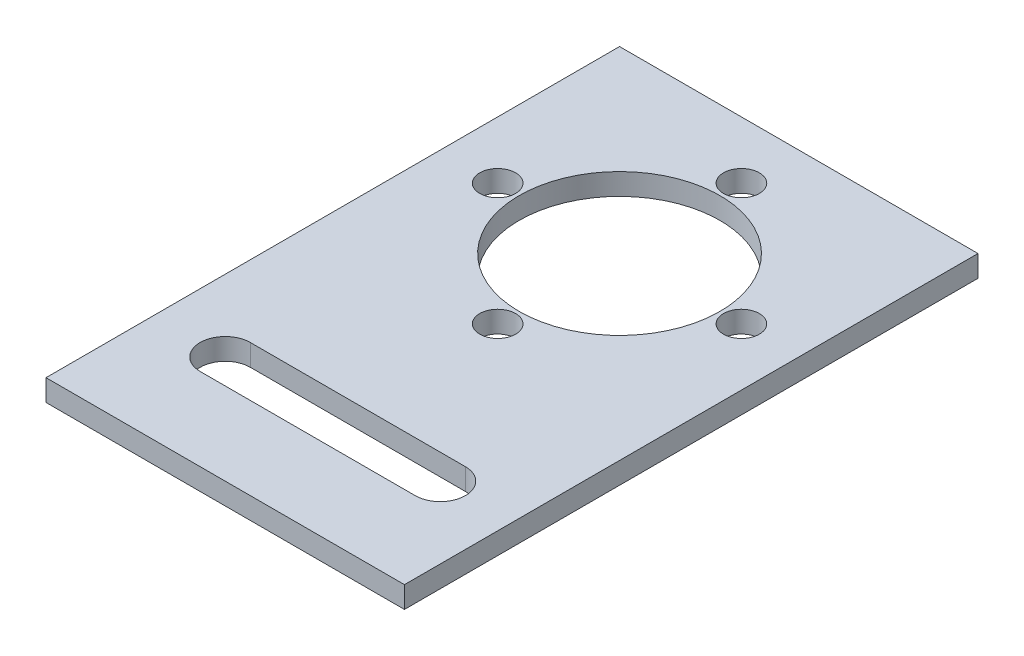
SolidWorks part; units mm, degrees
ref_plane "Front Plane" through (0, 0, 0) normal (0, 0, 1) x (1, 0, 0)
ref_plane "Top Plane" through (0, 0, 0) normal (0, 1, 0) x (1, 0, 0)
ref_plane "Right Plane" through (0, 0, 0) normal (1, 0, 0) x (0, 0, -1)
sketch "Sketch1" plane through (0, 0, 0) normal (0, 1, 0) x (1, 0, 0)
  line L0 (-15, -25) -> (15, -25) construction
  line L1 (-25, 40) -> (25, 40)
  line L2 (-25, 40) -> (-25, -40)
  line L3 (-25, -40) -> (25, -40)
  line L4 (25, 40) -> (25, -40)
  line L5 (-25, 40) -> (25, -40) construction
  line L6 (-25, -40) -> (25, 40) construction
  line L7 (-15, -21.5) -> (15, -21.5)
  line L8 (-15, -28.5) -> (15, -28.5)
  circle A0 centre (0, 15) radius 17 construction
  circle A1 centre (0, 32) radius 2.5
  circle A2 centre (17, 15) radius 2.5
  circle A3 centre (0, -2) radius 2.5
  circle A4 centre (-17, 15) radius 2.5
  arc A5 (-15, -21.5) -> (-15, -28.5) centre (-15, -25) ccw
  arc A6 (15, -28.5) -> (15, -21.5) centre (15, -25) ccw
  circle A7 centre (0, 15) radius 14
  point P0 (0, 0)
  point P8 (0, -25)
  dimension "D1" = 34
  dimension "D5" = 5
  dimension "D7" = 3.5
  dimension "D10" = 28
  dimension "D2" = 15
  dimension "D3" = 80
  dimension "D4" = 50
  dimension "D8" = 15
  dimension "D9" = 30
  dimension "D6" = 4
extrude "Boss-Extrude1" add sketch "Sketch1" along normal blind 3
